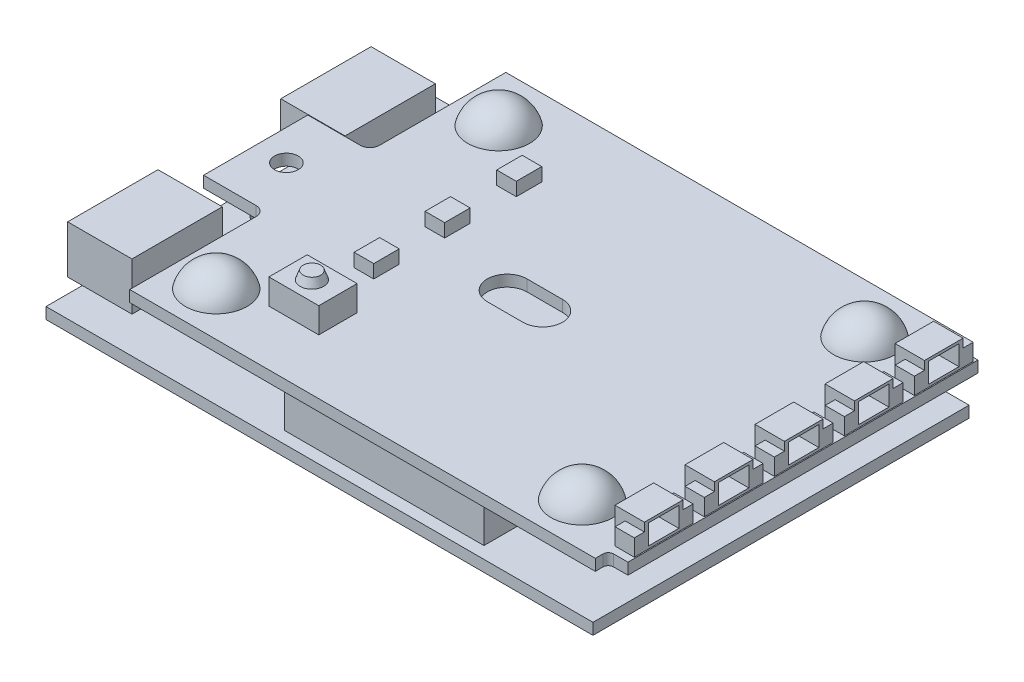
SolidWorks part; units mm, degrees
ref_plane "Front Plane" through (0, 0, 0) normal (0, 0, 1) x (1, 0, 0)
ref_plane "Top Plane" through (0, 0, 0) normal (0, 1, 0) x (1, 0, 0)
ref_plane "Right Plane" through (0, 0, 0) normal (1, 0, 0) x (0, 0, -1)
sketch "Sketch1" plane through (0, 0, 0) normal (0, 1, 0) x (1, 0, 0)
  line L1 (0, 0) -> (77.978, 0)
  line L2 (0, 0) -> (0, -53.6194)
  line L3 (0, -53.6194) -> (77.978, -53.6194)
  line L4 (77.978, 0) -> (77.978, -53.6194)
  dimension "D1" = 77.978
  dimension "D2" = 53.6194
extrude "Bottom Board" add sketch "Sketch1" along normal blind 1.6129
sketch "Sketch2" plane through (0, 1.6129, 0) normal (0, 1, 0) x (-1, 0, 0)
  line L0 (0, 0) -> (0, 53.6194) construction
  line L1 (2.0955, 5.1816) -> (-7.0739, 5.1816)
  line L2 (2.0955, 5.1816) -> (2.0955, 18.0594)
  line L3 (2.0955, 18.0594) -> (-7.0739, 18.0594)
  line L4 (-7.0739, 5.1816) -> (-7.0739, 18.0594)
  line L5 (-77.978, 0) -> (0, 0) construction
  dimension "D1" = 12.8778
  dimension "D2" = 9.1694
  dimension "D3" = 5.1816
  dimension "D4" = 2.0955
extrude "Connector Body" add sketch "Sketch2" along normal blind 6.8199
sketch "Sketch4" plane through (-2.0955, 0, 0) normal (-1, 0, 0) x (0, 0, 1)
  line L0 (5.1816, 8.4328) -> (5.1816, 1.6129) construction
  line L1 (5.7658, 7.8105) -> (8.3947, 7.8105)
  line L2 (5.7658, 7.8105) -> (5.7658, 5.2197)
  line L3 (5.7658, 5.2197) -> (8.3947, 5.2197)
  line L4 (8.3947, 7.8105) -> (8.3947, 5.2197)
  line L5 (5.1816, 8.4328) -> (18.0594, 8.4328) construction
  line L6 (8.7926, 7.8105) -> (8.7926, 5.2197)
  line L7 (8.7926, 5.2197) -> (11.4215, 5.2197)
  line L8 (11.4215, 7.8105) -> (11.4215, 5.2197)
  line L9 (8.7926, 7.8105) -> (11.4215, 7.8105)
  line L10 (11.8195, 7.8105) -> (11.8195, 5.2197)
  line L11 (11.8195, 5.2197) -> (14.4484, 5.2197)
  line L12 (14.4484, 7.8105) -> (14.4484, 5.2197)
  line L13 (11.8195, 7.8105) -> (14.4484, 7.8105)
  line L14 (14.8463, 7.8105) -> (14.8463, 5.2197)
  line L15 (14.8463, 5.2197) -> (17.4752, 5.2197)
  line L16 (17.4752, 7.8105) -> (17.4752, 5.2197)
  line L17 (14.8463, 7.8105) -> (17.4752, 7.8105)
  line L18 (5.7658, 4.826) -> (5.7658, 2.2352)
  line L19 (5.7658, 2.2352) -> (8.3947, 2.2352)
  line L20 (8.3947, 4.826) -> (8.3947, 2.2352)
  line L21 (5.7658, 4.826) -> (8.3947, 4.826)
  line L22 (8.7926, 4.826) -> (8.7926, 2.2352)
  line L23 (8.7926, 2.2352) -> (11.4215, 2.2352)
  line L24 (11.4215, 4.826) -> (11.4215, 2.2352)
  line L25 (8.7926, 4.826) -> (11.4215, 4.826)
  line L26 (11.8195, 4.826) -> (11.8195, 2.2352)
  line L27 (11.8195, 2.2352) -> (14.4484, 2.2352)
  line L28 (14.4484, 4.826) -> (14.4484, 2.2352)
  line L29 (11.8195, 4.826) -> (14.4484, 4.826)
  line L30 (14.8463, 4.826) -> (14.8463, 2.2352)
  line L31 (14.8463, 2.2352) -> (17.4752, 2.2352)
  line L32 (17.4752, 4.826) -> (17.4752, 2.2352)
  line L33 (14.8463, 4.826) -> (17.4752, 4.826)
  line L34 (18.0594, 8.4328) -> (18.0594, 1.6129) construction
  line L35 (17.4752, 7.4085) -> (18.0594, 7.4085) construction
  line L36 (5.7658, 7.5345) -> (5.1816, 7.5345) construction
  line L37 (7.8077, 7.8105) -> (7.8077, 8.4328)
  line L38 (7.8077, 2.2352) -> (7.8077, 1.6129)
  line L39 (5.1816, 1.6129) -> (18.0594, 1.6129) construction
  dimension "D1" = 2.6289
  dimension "D2" = 2.5908
  dimension "D3" = 0.5842
  dimension "D4" = 0.6223
  dimension "D5" = 4
  dimension "D6" = 2
extrude "Connector Holes" cut sketch "Sketch4" against normal blind 5.08 contours L4 L1 L2 L3 | L9 L6 L7 L8 | L13 L10 L11 L12 | L17 L14 L15 L16 | L33 L30 L31 L32 | L29 L26 L27 L28 | L25 L22 L23 L24 | L21 L18 L19 L20 region at (-2.0955, 6.5151, 7.0802) region at (-2.0955, 6.5151, 10.1071) region at (-2.0955, 6.5151, 13.1339) region at (-2.0955, 6.5151, 16.1608) region at (-2.0955, 3.5306, 7.0802) region at (-2.0955, 3.5306, 10.1071) region at (-2.0955, 3.5306, 13.1339) region at (-2.0955, 3.5306, 16.1608)
ref_plane "Center Plane" through (0, 0, 26.8097) normal (0, 0, -1) x (-1, 0, 0)
mirror "Connector Mirror" about plane through (0, 0, 26.8097) normal (0, 0, -1) of "Connector Holes", "Connector Body"
sketch "Sketch5" plane through (0, 1.6129, 0) normal (0, 1, 0) x (1, 0, 0)
  line L0 (77.978, -26.8097) -> (0, -26.8097) construction
  line L1 (77.978, -53.6194) -> (77.978, 0) construction
  line L2 (0, -18.0594) -> (0, -35.56) construction
  line L3 (2.9845, -26.8097) -> (2.9845, -21.4955) construction
  line L4 (36.0172, -26.8097) -> (36.0172, -8.1241) construction
  line L5 (0, -18.0594) -> (0, -35.56) construction
  circle A0 centre (4.68, -26.8097) radius 1.6955
  circle A1 centre (39.0652, -26.8097) radius 3.048
  dimension "D1" = 3.3909
  dimension "D3" = 6.096
  dimension "D2" = 2.9845
  dimension "D4" = 36.0172
extrude "Bottom Board Hole" cut sketch "Sketch5" against normal up to next
sketch "Sketch6" plane through (0, 1.6129, 0) normal (0, 1, 0) x (-1, 0, 0)
  line L0 (-77.978, 0) -> (0, 0) construction
  line L1 (-39.37, 1.7018) -> (-67.818, 1.7018)
  line L2 (-39.37, 1.7018) -> (-39.37, 7.2644)
  line L3 (-39.37, 7.2644) -> (-67.818, 7.2644)
  line L4 (-67.818, 1.7018) -> (-67.818, 7.2644)
  line L5 (-77.978, 53.6194) -> (-77.978, 0) construction
  line L6 (-32.2834, 46.355) -> (-60.7314, 46.355)
  line L7 (-32.2834, 46.355) -> (-32.2834, 51.9176)
  line L8 (-32.2834, 51.9176) -> (-60.7314, 51.9176)
  line L9 (-60.7314, 46.355) -> (-60.7314, 51.9176)
  line L10 (0, 18.0594) -> (0, 35.56) construction
  line L12 (-44.4047, 1.7018) -> (-44.4047, 0) construction
  line L13 (-37.561, 51.9176) -> (-37.561, 53.6194) construction
  line L14 (0, 53.6194) -> (-77.978, 53.6194) construction
  dimension "D1" = 28.448
  dimension "D2" = 5.5626
  dimension "D3" = 1.7018
  dimension "D4" = 10.16
  dimension "D5" = 28.448
  dimension "D6" = 5.5626
  dimension "D7" = 32.2834
extrude "Layer Connectors" add sketch "Sketch6" along normal blind 6.4516
sketch "Sketch7" plane through (0, 8.0645, 0) normal (0, 1, 0) x (1, 0, 0)
  line L0 (77.978, -53.6194) -> (77.978, 0) construction
  line L1 (78.3082, 0) -> (11.938, 0)
  line L2 (81.1022, -1.8542) -> (81.1022, -51.7652)
  line L3 (78.3082, -53.6194) -> (11.938, -53.6194)
  line L4 (11.938, 0) -> (11.938, -18.0086)
  line L5 (0, -18.0594) -> (0, -35.56) construction
  line L6 (77.978, 0) -> (0, 0) construction
  line L7 (0, -53.6194) -> (77.978, -53.6194) construction
  line L8 (15.6034, 0) -> (15.6034, -19.3802) construction
  line L9 (10.5664, -19.3802) -> (3.0861, -19.3802)
  line L10 (11.938, -35.6108) -> (11.938, -53.6194)
  line L11 (10.5664, -34.2392) -> (3.0861, -34.2392)
  line L12 (3.0861, -19.3802) -> (3.0861, -34.2392)
  line L13 (10.5664, -19.3802) -> (15.6034, -19.3802) construction
  line L14 (16.8171, -34.2392) -> (16.8171, -53.6194) construction
  line L15 (10.5664, -34.2392) -> (16.8171, -34.2392) construction
  line L16 (77.978, -26.8097) -> (0, -26.8097) construction
  line L17 (5.7658, -26.8097) -> (5.7658, -22.9762) construction
  line L18 (36.1061, -26.8097) -> (46.8249, -26.8097) construction
  line L19 (38.9318, -23.984) -> (43.9992, -23.984)
  line L20 (36.1061, -26.8097) -> (36.1061, -33.1542) construction
  line L21 (38.9318, -29.6354) -> (43.9992, -29.6355)
  line L22 (78.3082, -53.6194) -> (78.3082, -52.5272)
  line L23 (81.1022, -51.7652) -> (79.0702, -51.7652)
  line L25 (81.1022, -1.8542) -> (79.0702, -1.8542)
  line L26 (78.3082, 0) -> (78.3082, -1.0922)
  arc A0 (11.938, -18.0086) -> (10.5664, -19.3802) centre (10.5664, -18.0086) cw
  arc A1 (10.5664, -34.2392) -> (11.938, -35.6108) centre (10.5664, -35.6108) cw
  circle A2 centre (7.4613, -26.8097) radius 1.6955
  circle A3 centre (4.68, -26.8097) radius 1.6955 construction
  arc A4 (38.9318, -29.6354) -> (38.9318, -23.984) centre (38.9318, -26.8097) cw
  arc A5 (43.9992, -23.984) -> (43.9992, -29.6355) centre (43.9992, -26.8097) cw
  arc A6 (79.0702, -1.8542) -> (78.3082, -1.0922) centre (79.0702, -1.0922) cw
  arc A7 (79.0702, -51.7652) -> (78.3082, -52.5272) centre (79.0702, -52.5272) ccw
  point P45 (78.3082, -1.8542)
  dimension "D5" = 1.3716
  dimension "D6" = 1.3716
  dimension "D13" = 0.762
  dimension "D1" = 3.1242
  dimension "D2" = 11.938
  dimension "D3" = 19.3802
  dimension "D4" = 3.0861
  dimension "D7" = 2.6797
  dimension "D8" = 5.6515
  dimension "D9" = 10.7188
  dimension "D10" = 33.02
  dimension "D11" = 2.794
  dimension "D12" = 1.8542
extrude "Top Board" add sketch "Sketch7" along normal blind 1.6129
sketch "Sketch8" plane through (0, 9.6774, 0) normal (0, 1, 0) x (1, 0, 0)
  line L1 (80.9498, -2.3876) -> (78.2066, -2.3876)
  line L2 (80.9498, -2.3876) -> (80.9498, -10.7696)
  line L3 (80.9498, -10.7696) -> (78.2066, -10.7696)
  line L4 (78.2066, -2.3876) -> (78.2066, -10.7696)
  line L5 (78.3082, 0) -> (11.938, 0) construction
  line L6 (81.1022, -51.7652) -> (81.1022, -1.8542) construction
  dimension "D1" = 2.7432
  dimension "D2" = 8.382
  dimension "D3" = 2.3876
  dimension "D4" = 0.1524
extrude "Maker Connector Sides" add sketch "Sketch8" along normal blind 2.3876
sketch "Sketch9" plane through (0, 12.065, 0) normal (0, 1, 0) x (1, 0, 0)
  line L0 (80.9498, -10.7696) -> (80.9498, -2.3876) construction
  line L1 (80.9498, -3.8227) -> (76.7588, -3.8227)
  line L2 (80.9498, -3.8227) -> (80.9498, -9.3345)
  line L3 (80.9498, -9.3345) -> (76.7588, -9.3345)
  line L4 (76.7588, -3.8227) -> (76.7588, -9.3345)
  line L6 (78.7411, -2.3876) -> (78.7411, -3.8227) construction
  line L7 (80.9498, -2.3876) -> (78.2066, -2.3876) construction
  line L9 (78.7411, -9.3345) -> (78.7411, -10.7696) construction
  line L10 (78.2066, -10.7696) -> (80.9498, -10.7696) construction
  dimension "D1" = 5.5118
  dimension "D2" = 4.191
extrude "Marker Connector Box" add sketch "Sketch9" along normal blind 1.2192
sketch "Sketch10" plane through (0, 9.6774, 0) normal (0, 1, 0) x (1, 0, 0)
  line L0 (76.7588, -9.3345) -> (78.2066, -9.3345) construction
  line L1 (78.2066, -3.8227) -> (76.7588, -3.8227) construction
  line L2 (76.7588, -3.8227) -> (76.7588, -9.3345) construction
  line L3 (76.7588, -9.3345) -> (78.2066, -9.3345)
  line L4 (78.2066, -3.8227) -> (76.7588, -3.8227)
  line L5 (76.7588, -3.8227) -> (76.7588, -9.3345)
  line L10 (78.2066, -3.8227) -> (76.7588, -3.8227)
  line L11 (78.2066, -9.3345) -> (78.2066, -3.8227)
  line L12 (76.7588, -9.3345) -> (78.2066, -9.3345)
  line L13 (76.7588, -3.8227) -> (76.7588, -9.3345)
  line L14 (78.2066, -3.8227) -> (76.7588, -3.8227)
  line L15 (78.2066, -9.3345) -> (78.2066, -3.8227)
  line L16 (76.7588, -9.3345) -> (78.2066, -9.3345)
  line L17 (76.7588, -3.8227) -> (76.7588, -9.3345)
  line M11 (78.2066, -10.7696) -> (78.2066, -2.3876)
  dimension "D1" = 0
extrude "Marker Connector Rear" add sketch "Sketch10" along normal up to body contours L4 L5 L3 M11 region at (77.4827, 9.6774, 6.5786)
sketch "Sketch11" plane through (81.1022, 0, 0) normal (1, 0, 0) x (0, 0, -1)
  line L0 (-9.3345, 13.2842) -> (-9.3345, 12.065) construction
  line L1 (-8.7376, 12.9032) -> (-4.4196, 12.9032)
  line L2 (-8.7376, 12.9032) -> (-8.7376, 10.0584)
  line L3 (-8.7376, 10.0584) -> (-4.4196, 10.0584)
  line L4 (-4.4196, 12.9032) -> (-4.4196, 10.0584)
  line L5 (-8.7376, 11.497) -> (-9.3345, 11.497) construction
  line L6 (-4.4196, 12.3526) -> (-3.8227, 12.3526) construction
  line L7 (-3.8227, 13.2842) -> (-3.8227, 12.065) construction
  line L8 (-9.3345, 13.2842) -> (-3.8227, 13.2842) construction
  line L10 (-7.3098, 10.0584) -> (-7.3098, 9.6774) construction
  line L11 (-51.7652, 9.6774) -> (-1.8542, 9.6774) construction
  line L12 (-7.3098, 13.2842) -> (-7.3098, 12.9032) construction
  dimension "D1" = 0.5969
  dimension "D2" = 0.381
extrude "Marker Connector " cut sketch "Sketch11" against normal blind 3.175
pattern_linear "Maker Connectors Pattern" count 5 spacing 9.9822 along (0, 0, 1) of "Marker Connector Box", "Marker Connector ", "Maker Connector Sides", "Marker Connector Rear"
sketch "Sketch12" plane through (0, 9.6774, 0) normal (0, 1, 0) x (-1, 0, 0)
  line L0 (-13.589, 7.0866) -> (-13.589, -6.6902) construction
  line L1 (-11.938, 0) -> (-11.938, 18.0086) construction
  line L2 (-17.9959, 2.6797) -> (-29.745, 2.6797) construction
  line L3 (-78.3082, 0) -> (-11.938, 0) construction
  circle A0 centre (-17.9959, 7.0866) radius 4.4069
  dimension "D1" = 8.8138
  dimension "D2" = 1.651
  dimension "D3" = 2.6797
extrude "Glue Dome" add sketch "Sketch12" along normal blind 3.4036
fillet "Glue Dome Fillet" radius 4.5415 1 edges at (17.9959, 13.081, 11.4935)
pattern_linear "Glue pattern" count 2 spacing 40.259 along (0, 0, 1) count 2 spacing 52.1462 along (1, 0, 0) of "Glue Dome Fillet", "Glue Dome"
sketch "Sketch13" plane through (0, 9.6774, 0) normal (0, 1, 0) x (-1, 0, 0)
  line L0 (-78.3082, 0) -> (-11.938, 0) construction
  line L1 (-25.2349, 10.9728) -> (-28.0289, 10.9728)
  line L2 (-25.2349, 10.9728) -> (-25.2349, 14.605)
  line L3 (-25.2349, 14.605) -> (-28.0289, 14.605)
  line L4 (-28.0289, 10.9728) -> (-28.0289, 14.605)
  line L5 (-3.0861, 19.3802) -> (-3.0861, 34.2392) construction
  line L7 (-25.2349, 21.1836) -> (-28.0289, 21.1836)
  line L8 (-25.2349, 21.1836) -> (-25.2349, 24.8158)
  line L9 (-25.2349, 24.8158) -> (-28.0289, 24.8158)
  line L10 (-28.0289, 21.1836) -> (-28.0289, 24.8158)
  line L11 (-25.2349, 31.2928) -> (-28.0289, 31.2928)
  line L12 (-25.2349, 31.2928) -> (-25.2349, 34.925)
  line L13 (-25.2349, 34.925) -> (-28.0289, 34.925)
  line L14 (-28.0289, 31.2928) -> (-28.0289, 34.925)
  dimension "D1" = 2.794
  dimension "D2" = 3.6322
  dimension "D3" = 10.9728
  dimension "D4" = 22.1488
  dimension "D5" = 24.8158
  dimension "D6" = 34.925
extrude "LEDs" add sketch "Sketch13" along normal blind 1.905
sketch "Sketch14" plane through (0, 9.6774, 0) normal (0, 1, 0) x (-1, 0, 0)
  line L0 (-11.938, 53.6194) -> (-78.3082, 53.6194) construction
  line L1 (-23.9014, 40.2844) -> (-31.0134, 40.2844)
  line L2 (-23.9014, 40.2844) -> (-23.9014, 45.7454)
  line L3 (-23.9014, 45.7454) -> (-31.0134, 45.7454)
  line L4 (-31.0134, 40.2844) -> (-31.0134, 45.7454)
  line L5 (-81.1022, 51.7652) -> (-81.1022, 1.8542) construction
  dimension "D1" = 7.112
  dimension "D2" = 5.461
  dimension "D3" = 7.874
  dimension "D4" = 50.0888
extrude "IR receiver base" add sketch "Sketch14" along normal blind 3.6068
sketch "Sketch16" plane through (0, 13.2842, 0) normal (0, 1, 0) x (-1, 0, 0)
  line L0 (-27.305, 40.2844) -> (-27.305, 45.7454) construction
  line L3 (-31.0134, 40.2844) -> (-23.9014, 40.2844) construction
  line L4 (-23.9014, 45.7454) -> (-31.0134, 45.7454) construction
  line L5 (-28.9814, 43.0149) -> (-28.9814, 38.6964) construction
  line L6 (-23.9014, 40.2844) -> (-23.9014, 45.7454) construction
  circle A0 centre (-27.305, 43.0149) radius 1.6764
  circle A1 centre (-27.305, 43.0149) radius 1.2446 construction
  dimension "D1" = 3.3528
  dimension "D2" = 2.4892
  dimension "D3" = 5.08
ref_plane "Plane for IR receiver" through (0, 14.4526, 0) normal (0, 1, 0) x (-1, 0, 0)
sketch "Sketch17" plane through (0, 14.4526, 0) normal (0, 1, 0) x (-1, 0, 0)
  circle A0 centre (-27.305, 43.0149) radius 1.2446 construction
  circle A3 centre (-27.305, 43.0149) radius 1.2446
loft "IR receiver" add profiles "Sketch16", "Sketch17" connector at (28.1584, 13.2842, 44.4578) connector at (27.9456, 14.4526, 44.082)
sketch "Sketch18" plane through (0, 0, 0) normal (0, -1, 0) x (1, 0, 0)
  line L0 (0, 53.6194) -> (77.978, 53.6194) construction
  line L1 (15.2908, 49.5554) -> (18.0848, 49.5554)
  line L2 (15.2908, 49.5554) -> (15.2908, 44.5262)
  line L3 (15.2908, 44.5262) -> (18.0848, 44.5262)
  line L4 (18.0848, 49.5554) -> (18.0848, 44.5262)
  line L5 (0, 0) -> (0, 53.6194) construction
  line L6 (15.2908, 42.7228) -> (18.0848, 42.7228)
  line L7 (15.2908, 42.7228) -> (15.2908, 37.6936)
  line L8 (15.2908, 37.6936) -> (18.0848, 37.6936)
  line L9 (18.0848, 42.7228) -> (18.0848, 37.6936)
  line L10 (77.978, 0) -> (0, 0) construction
  line L11 (20.32, 36.0934) -> (23.114, 36.0934)
  line L12 (20.32, 36.0934) -> (20.32, 31.0642)
  line L13 (20.32, 31.0642) -> (23.114, 31.0642)
  line L14 (23.114, 36.0934) -> (23.114, 31.0642)
  dimension "D1" = 2.794
  dimension "D2" = 5.0292
  dimension "D3" = 4.064
  dimension "D4" = 15.2908
  dimension "D5" = 2.794
  dimension "D6" = 5.0292
  dimension "D7" = 37.6936
  dimension "D8" = 2.794
  dimension "D9" = 5.0292
  dimension "D10" = 20.32
  dimension "D11" = 17.526
extrude "Back components" add sketch "Sketch18" along normal blind 2.4892
sketch "Sketch19" plane through (0, 0, 0) normal (0, -1, 0) x (1, 0, 0)
  line L0 (0, 53.6194) -> (77.978, 53.6194) construction
  line L1 (36.3093, 43.5864) -> (38.0873, 43.5864)
  line L2 (36.3093, 43.5864) -> (36.3093, 40.513)
  line L3 (36.3093, 40.513) -> (38.0873, 40.513)
  line L4 (38.0873, 43.5864) -> (38.0873, 40.513)
  line L5 (77.978, 53.6194) -> (77.978, 0) construction
  line L6 (40.3606, 37.338) -> (42.1386, 37.338)
  line L7 (40.3606, 37.338) -> (40.3606, 34.2646)
  line L8 (40.3606, 34.2646) -> (42.1386, 34.2646)
  line L9 (42.1386, 37.338) -> (42.1386, 34.2646)
  line L10 (51.3334, 18.923) -> (53.1114, 18.923)
  line L11 (51.3334, 18.923) -> (51.3334, 15.8496)
  line L12 (51.3334, 15.8496) -> (53.1114, 15.8496)
  line L13 (53.1114, 18.923) -> (53.1114, 15.8496)
  line L14 (77.978, 0) -> (0, 0) construction
  line L15 (34.9758, 15.24) -> (36.7538, 15.24)
  line L16 (34.9758, 15.24) -> (34.9758, 12.1666)
  line L17 (34.9758, 12.1666) -> (36.7538, 12.1666)
  line L18 (36.7538, 15.24) -> (36.7538, 12.1666)
  line L19 (41.3004, 15.24) -> (43.0784, 15.24)
  line L20 (41.3004, 15.24) -> (41.3004, 12.1666)
  line L21 (41.3004, 12.1666) -> (43.0784, 12.1666)
  line L22 (43.0784, 15.24) -> (43.0784, 12.1666)
  line L23 (74.295, 50.7619) -> (76.073, 50.7619)
  line L24 (74.295, 50.7619) -> (74.295, 47.6885)
  line L25 (74.295, 47.6885) -> (76.073, 47.6885)
  line L26 (76.073, 50.7619) -> (76.073, 47.6885)
  line L27 (70.231, 10.287) -> (70.231, 12.065)
  line L28 (70.231, 10.287) -> (73.3044, 10.287)
  line L29 (73.3044, 10.287) -> (73.3044, 12.065)
  line L30 (70.231, 12.065) -> (73.3044, 12.065)
  line L31 (70.231, 6.2484) -> (70.231, 8.0264)
  line L32 (70.231, 6.2484) -> (73.3044, 6.2484)
  line L33 (73.3044, 6.2484) -> (73.3044, 8.0264)
  line L34 (70.231, 8.0264) -> (73.3044, 8.0264)
  line L35 (23.4315, 27.3558) -> (25.2095, 27.3558)
  line L36 (23.4315, 27.3558) -> (23.4315, 24.2824)
  line L37 (23.4315, 24.2824) -> (25.2095, 24.2824)
  line L38 (25.2095, 27.3558) -> (25.2095, 24.2824)
  line L39 (16.9799, 12.0904) -> (18.7579, 12.0904)
  line L40 (16.9799, 12.0904) -> (16.9799, 9.017)
  line L41 (16.9799, 9.017) -> (18.7579, 9.017)
  line L42 (18.7579, 12.0904) -> (18.7579, 9.017)
  line L43 (0, 0) -> (0, 53.6194) construction
  point P34 (0, 0)
  dimension "D1" = 1.778
  dimension "D2" = 3.0734
  dimension "D3" = 10.033
  dimension "D4" = 39.8907
  dimension "D5" = 1.778
  dimension "D6" = 16.2814
  dimension "D7" = 35.8394
  dimension "D8" = 18.923
  dimension "D9" = 26.6446
  dimension "D10" = 43.0022
  dimension "D11" = 15.24
  dimension "D12" = 36.6776
  dimension "D13" = 5.9309
  dimension "D14" = 3.683
  dimension "D15" = 12.065
  dimension "D16" = 7.747
  dimension "D17" = 8.0264
  dimension "D18" = 27.3558
  dimension "D19" = 25.2095
  dimension "D20" = 18.7579
  dimension "D21" = 12.0904
extrude "Bottom caps" add sketch "Sketch19" along normal blind 1.7526
sketch "Sketch20" plane through (0, 0, 0) normal (0, -1, 0) x (1, 0, 0)
  line L0 (77.978, 0) -> (0, 0) construction
  line L1 (26.924, 6.477) -> (31.8516, 6.477)
  line L2 (26.924, 6.477) -> (26.924, 2.6162)
  line L3 (26.924, 2.6162) -> (31.8516, 2.6162)
  line L4 (31.8516, 6.477) -> (31.8516, 2.6162)
  line L5 (0, 0) -> (0, 53.6194) construction
  dimension "D1" = 4.9276
  dimension "D2" = 3.8608
  dimension "D3" = 6.477
  dimension "D4" = 31.8516
extrude "Chip" add sketch "Sketch20" along normal blind 1.5875
sketch "Sketch21" plane through (0, 0, 0) normal (0, -1, 0) x (1, 0, 0)
  line L0 (77.978, 0) -> (0, 0) construction
  line L1 (54.102, 12.0777) -> (55.5498, 12.0777)
  line L2 (54.102, 12.0777) -> (54.102, 10.0203)
  line L3 (54.102, 10.0203) -> (55.5498, 10.0203)
  line L4 (55.5498, 12.0777) -> (55.5498, 10.0203)
  line L5 (77.978, 53.6194) -> (77.978, 0) construction
  line L6 (57.3278, 12.0777) -> (58.7756, 12.0777)
  line L7 (57.3278, 12.0777) -> (57.3278, 10.0203)
  line L8 (57.3278, 10.0203) -> (58.7756, 10.0203)
  line L9 (58.7756, 12.0777) -> (58.7756, 10.0203)
  dimension "D1" = 1.4478
  dimension "D2" = 2.0574
  dimension "D3" = 12.0777
  dimension "D4" = 23.876
  dimension "D5" = 20.6502
extrude "FLs" add sketch "Sketch21" along normal blind 0.9779
